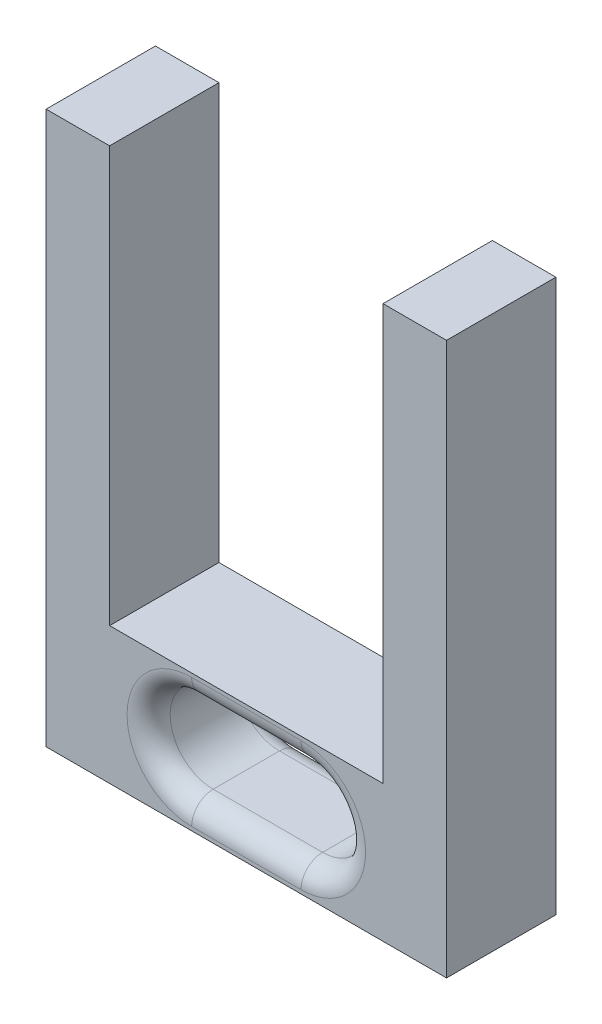
SolidWorks part; units mm, degrees
ref_plane "XY" through (0, 0, 0) normal (0, 0, 1) x (1, 0, 0)
ref_plane "XZ" through (0, 0, 0) normal (0, 1, 0) x (1, 0, 0)
ref_plane "YZ" through (0, 0, 0) normal (1, 0, 0) x (0, 0, -1)
ref_axis "X" through (-51.15, 0, 0) along (1, 0, 0)
ref_axis "Y" through (0, -134.6835, 0) along (0, 1, 0)
ref_axis "Z" through (0, 0, 26.67) along (0, 0, -1)
sketch "Sketch1" plane through (0, 0, 0) normal (0, 0, 1) x (1, 0, 0)
  line L0 (-46.5, 0) -> (-31.75, 0)
  line L1 (-31.75, 0) -> (-31.75, -96.52)
  line L2 (-31.75, -96.52) -> (31.75, -96.52)
  line L3 (31.75, -96.52) -> (31.75, 0)
  line L4 (-46.5, 0) -> (-46.5, -128.27)
  line L5 (-46.5, -128.27) -> (46.5, -128.27)
  line L6 (46.5, -128.27) -> (46.5, 0)
  line L7 (46.5, 0) -> (31.75, 0)
  line L8 (0, 0) -> (0, -96.52) construction
  line L9 (-31.75, 0) -> (31.75, 0) construction
  line L10 (-12.7, -112.395) -> (12.7, -112.395) construction
  line L11 (-12.7, -102.395) -> (12.7, -102.395)
  line L12 (-12.7, -122.395) -> (12.7, -122.395)
  line L13 (0, -96.52) -> (0, -128.27) construction
  arc A0 (-12.7, -102.395) -> (-12.7, -122.395) centre (-12.7, -112.395) ccw
  arc A1 (12.7, -122.395) -> (12.7, -102.395) centre (12.7, -112.395) ccw
  point P12 (0, -112.395)
  dimension "D3" = 10
  dimension "D1" = 96.52
  dimension "D2" = 63.5
  dimension "D4" = 31.75
  dimension "D5" = 25.4
  dimension "D6" = 93
extrude "Boss-Extrude1" add sketch "Sketch1" along normal blind 25.4
fillet "Fillet1" radius 5 8 edges at (22.7, -112.395, 0) (0, -122.395, 0) (-22.7, -112.395, 0) (-22.7, -112.395, 25.4) (0, -102.395, 25.4) (22.7, -112.395, 25.4) (0, -102.395, 0) (0, -122.395, 25.4)
